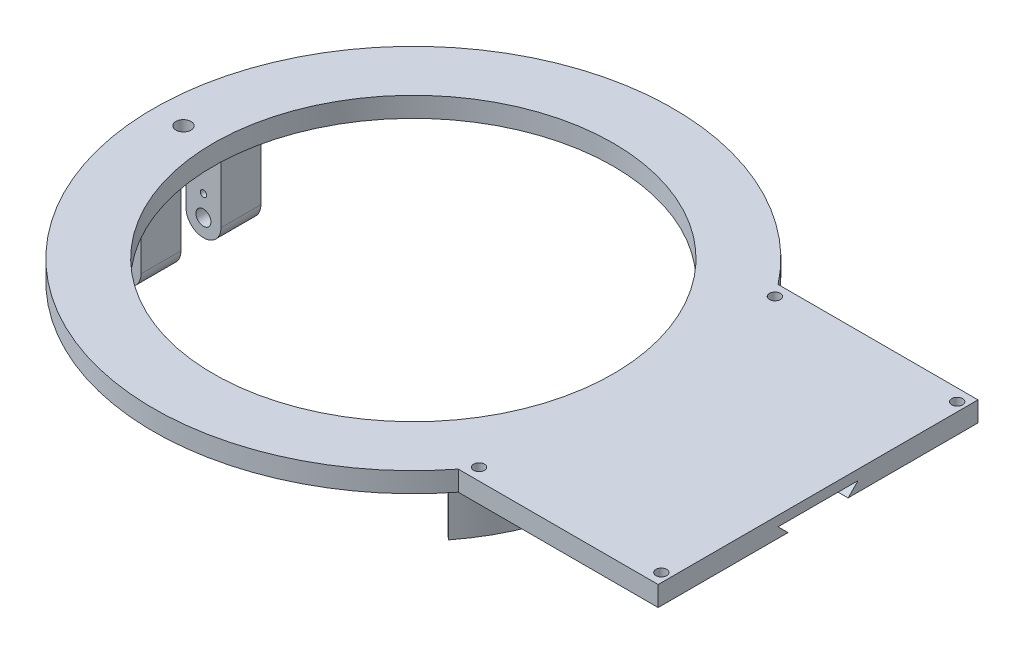
SolidWorks part; units mm, degrees
ref_plane "Front Plane" through (0, 0, 0) normal (0, 0, 1) x (1, 0, 0)
ref_plane "Top Plane" through (0, 0, 0) normal (0, 1, 0) x (1, 0, 0)
ref_plane "Right Plane" through (0, 0, 0) normal (1, 0, 0) x (0, 0, -1)
sketch "Sketch1" plane through (0, 0, 0) normal (0, 0, 1) x (1, 0, 0)
  line L0 (0, -6.6146) -> (0, 6.6146) construction
  line L1 (-63.5, 0) -> (-63.5, -6.35)
  line L2 (-63.5, -6.35) -> (-82.55, -6.35)
  line L3 (-82.55, -6.35) -> (-82.55, 0)
  line L4 (-82.55, 0) -> (-63.5, 0)
  point P4 (0, 0)
  dimension "D1" = 19.05
  dimension "D2" = 6.35
  dimension "D3" = 127
revolve "Revolve1" add sketch "Sketch1" angle 360 about L0
sketch "Sketch2" plane through (0, 0, 0) normal (0, 0, 1) x (1, 0, 0)
  line L5 (-73.025, -6.35) -> (-73.025, -28.448) construction
  line L6 (-73.025, -28.448) -> (-73.025, -34.0043) construction
  line L7 (0, 0) -> (0, -6.35) construction
  line L8 (0, -6.35) -> (-73.025, -6.35) construction
  line L9 (-67.4688, -28.448) -> (-67.4688, -6.35)
  line L10 (-67.4688, -6.35) -> (-78.5812, -6.35)
  line L11 (-78.5812, -28.448) -> (-78.5812, -6.35)
  circle A2 centre (-73.025, -28.448) radius 2.3813
  arc A3 (-78.5812, -28.448) -> (-67.4688, -28.448) centre (-73.025, -28.448) ccw
  arc A4 (-67.4688, -28.448) -> (-73.025, -22.8918) centre (-73.025, -28.448) ccw construction
  arc A5 (-73.025, -22.8918) -> (-78.5812, -28.448) centre (-73.025, -28.448) ccw construction
  dimension "D3" = 3.175
  dimension "D4" = 4.7625
  dimension "D1" = 6.35
  dimension "D2" = 22.098
  dimension "D5" = 73.025
extrude "Boss-Extrude1" add sketch "Sketch2" along normal blind 19.05 and the other way blind 19.05 contours A3 L9 L10 L11 | A2
sketch "Sketch3" plane through (0, -6.35, 0) normal (0, -1, 0) x (1, 0, 0)
  line L0 (0, 0) -> (-78.5812, 0) construction
  line L1 (-78.5812, -19.05) -> (-78.5812, 19.05) construction
  line L2 (-78.5812, -6.35) -> (-78.5812, 6.35)
  line L3 (-78.5812, 6.35) -> (-58.5257, 6.35)
  line L4 (-58.5257, 6.35) -> (-58.5257, -6.35)
  line L5 (-78.5812, -6.35) -> (-58.5257, -6.35)
  point P9 (-58.5257, 0)
  dimension "D1" = 12.7
extrude "Cut-Extrude1" cut sketch "Sketch3" along normal through all
hole_wizard "Tap Drill for #3-48 Tap1" positions "Sketch4" profile "Sketch5" hole size "#3-48" standard "ANSI Inch" end condition through all
sketch "Sketch4" plane through (0, 0, -19.05) normal (0, 0, -1) x (-1, 0, 0)
  line L0 (73.025, -6.35) -> (73.025, -12.7) construction
  line L1 (67.4688, -6.35) -> (78.5812, -6.35) construction
  point P2 (73.025, -12.7)
  point P11 (73.025, -21.844)
  dimension "D2" = 9.144
  dimension "D3" = 6.35
sketch "Sketch5" plane through (-73.025, -21.844, -19.05) normal (1, 0, 0) x (0, 1, 0)
  line L0 (0, 0) -> (0, 101.6)
  line L1 (0, 101.6) -> (0.9969, 101.6)
  line L2 (0.9969, 101.6) -> (0.9969, 0)
  line L5 (0.9969, 0) -> (0, 0)
  line L11 (0, -6.35) -> (0, 107.95) construction
  dimension "Thru Hole Dia." = 1.9939
  dimension "Thru Hole Depth" = 101.6
sketch "Sketch6" plane through (0, 0, 0) normal (0, 1, 0) x (1, 0, 0)
  line L0 (0, 0) -> (82.55, 0) construction
  line L1 (65.0681, -50.8) -> (128.5681, -50.8)
  line L2 (65.0681, 0) -> (128.5681, 0) construction
  line L3 (65.0681, -50.8) -> (65.0681, 50.8)
  line L4 (65.0681, 50.8) -> (128.5681, 50.8)
  line L5 (128.5681, -50.8) -> (128.5681, 50.8)
  circle A0 centre (0, 0) radius 82.55 construction
  circle A1 centre (0, 0) radius 82.55 construction
  dimension "D1" = 101.6
  dimension "D2" = 63.5
extrude "Boss-Extrude2" add sketch "Sketch6" against normal up to surface (6.35 mm away) up to face at (0, -6.35, -63.5)
sketch "Sketch7" plane through (0, -6.35, 0) normal (0, -1, 0) x (1, 0, 0)
  line L0 (128.5681, 0) -> (96.8181, 0) construction
  line L1 (128.5681, -50.8) -> (128.5681, 50.8) construction
  line L2 (128.5681, -50.8) -> (65.0681, 50.8) construction
  line L4 (67.8621, 46.99) -> (125.7741, 46.99) construction
  line L5 (67.8621, 46.99) -> (67.8621, -46.99) construction
  line L6 (67.8621, -46.99) -> (125.7741, -46.99) construction
  line L7 (125.7741, 46.99) -> (125.7741, -46.99) construction
  line L8 (67.8621, 46.99) -> (125.7741, -46.99) construction
  line L9 (67.8621, -46.99) -> (125.7741, 46.99) construction
  circle A0 centre (125.7741, -46.99) radius 1.4288
  circle A1 centre (67.8621, -46.99) radius 1.4288
  circle A2 centre (67.8621, 46.99) radius 1.4288
  circle A3 centre (125.7741, 46.99) radius 1.4288
  point P10 (96.8181, 0)
  dimension "D3" = 2.8575
  dimension "D1" = 57.912
  dimension "D2" = 93.98
sketch "Sketch8" plane through (128.5681, 0, 0) normal (1, 0, 0) x (0, 0, -1)
  line L0 (0, 0) -> (0, -3.175) construction
  line L1 (-50.8, 0) -> (50.8, 0) construction
  line L2 (12.7, -3.175) -> (-12.7, -3.175)
  line L3 (-12.7, -3.175) -> (-8.7592, -7.1158)
  line L4 (-8.7592, -7.1158) -> (8.7592, -7.1158)
  line L5 (0, -7.1158) -> (0, -3.175) construction
  line L6 (12.7, -3.175) -> (8.7592, -7.1158)
  dimension "D1" = 12.7
  dimension "D2" = 45
  dimension "D3" = 3.175
extrude "Cut-Extrude2" cut sketch "Sketch8" against normal blind 50.8
sketch "Sketch9" plane through (0, -6.35, 0) normal (0, -1, 0) x (1, 0, 0)
  line L0 (0, 0) -> (65.0681, 50.8) construction
  line L1 (0, 0) -> (65.0681, -50.8) construction
  line L2 (51.2937, 40.046) -> (50.0524, 39.0769)
  line L3 (50.0524, -39.0769) -> (51.2937, -40.046)
  arc A1 (50.0524, 39.0769) -> (50.0524, -39.0769) centre (0, 0) cw
  circle A2 centre (0, 0) radius 63.5 construction
  arc A3 (51.2937, 40.046) -> (51.2937, -40.046) centre (0, 0) cw
  dimension "D1" = 1.5748
extrude "Boss-Extrude4" add sketch "Sketch9" along normal blind 25.4
fillet "Fillet1" radius 4.7625 1 edges at (65.0748, -6.35, 0)
hole_wizard "Tap Drill for #8-32 Tap1" positions "Sketch10" profile "Sketch11" hole size "#8-32" standard "ANSI Inch" end condition up to next
sketch "Sketch10" plane through (0, -6.35, 0) normal (0, -1, 0) x (-1, 0, 0)
  point P0 (-67.8621, -46.99)
  point P3 (-125.7741, -46.99)
  point P6 (-125.7741, 46.99)
  point P9 (-67.8621, 46.99)
sketch "Sketch11" plane through (67.8621, -6.35, 46.99) normal (1, 0, 0) x (0, 0, -1)
  line L0 (0, 0) -> (0, 6.35)
  line L1 (0, 6.35) -> (1.7272, 6.35)
  line L2 (1.7272, 6.35) -> (1.7272, 0)
  line L5 (1.7272, 0) -> (0, 0)
  line L11 (0, -6.35) -> (0, 107.95) construction
  dimension "Thru Hole Dia." = 3.4544
  dimension "Thru Hole Depth" = 6.35
sketch "Sketch12" plane through (0, -6.35, 0) normal (0, -1, 0) x (1, 0, 0)
  line L0 (-67.4688, -19.05) -> (-78.5812, -19.05) construction
  arc A0 (62.0655, -39.869) -> (-71.2654, -19.05) centre (0, 0) cw
  arc A1 (60.7405, -39.0179) -> (-69.7441, -18.6433) centre (0, 0) cw
  arc A2 (63.3905, -40.7201) -> (-72.7868, -19.4567) centre (0, 0) cw
  arc A3 (60.7405, -39.0179) -> (63.3905, -40.7201) centre (62.0655, -39.869) cw
  arc A4 (-69.7441, -18.6433) -> (-72.7868, -19.4567) centre (-71.2654, -19.05) ccw
  line M5 (-67.4688, -19.05) -> (-78.5812, -19.05)
  dimension "D1" = 1.5748
  dimension "D2" = 1.5748
extrude "Cut-Extrude3" cut sketch "Sketch12" against normal blind 3.175 contours A4 A2 A3 A1 M5 region at (62.1187, -6.35, -39.7862)
hole_wizard "#12 (0.189) Diameter Hole1" positions "Sketch13" profile "Sketch14" hole size "#12" standard "ANSI Inch" end condition up to next
sketch "Sketch13" plane through (0, -6.35, 0) normal (0, -1, 0) x (-1, 0, 0)
  circle A0 centre (0, 0) radius 73.025
  point P4 (73.025, 0)
sketch "Sketch14" plane through (-73.025, -6.35, 0) normal (1, 0, 0) x (0, 0, -1)
  line L0 (0, 0) -> (0, 6.35)
  line L1 (0, 6.35) -> (2.4003, 6.35)
  line L2 (2.4003, 6.35) -> (2.4003, 0)
  line L5 (2.4003, 0) -> (0, 0)
  line L11 (0, -6.35) -> (0, 107.95) construction
  dimension "Thru Hole Dia." = 4.8006
  dimension "Thru Hole Depth" = 6.35
